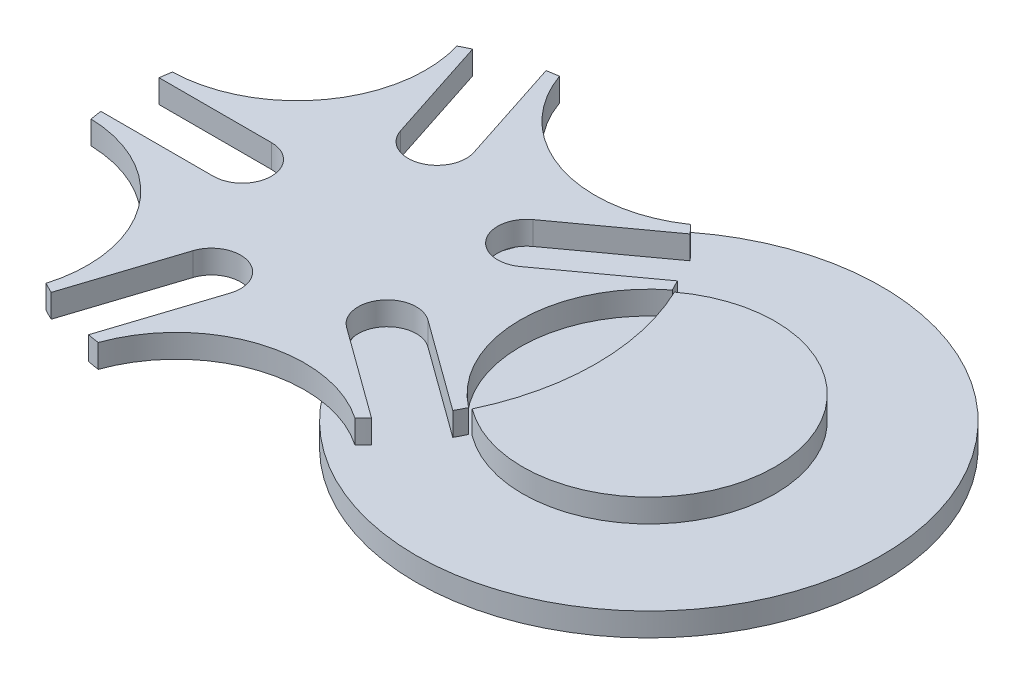
SolidWorks part; units mm, degrees
ref_plane "Front Plane" through (0, 0, 0) normal (0, 0, 1) x (1, 0, 0)
ref_plane "Top Plane" through (0, 0, 0) normal (0, 1, 0) x (1, 0, 0)
ref_plane "Right Plane" through (0, 0, 0) normal (1, 0, 0) x (0, 0, -1)
sketch "foundational triangle" plane through (0, 0, 0) normal (0, 1, 0) x (1, 0, 0)
  line L0 (0, 0) -> (20.549, 14.9297) construction
  line L1 (20.549, 14.9297) -> (31.3961, 0) construction
  line L2 (31.3961, 0) -> (0, 0) construction
  dimension "D1" = 90
  dimension "D2" = 25.4
  dimension "D3" = 36
sketch "main circles" plane through (0, 0, 0) normal (0, 1, 0) x (1, 0, 0)
  circle A0 centre (0, 0) radius 25.4
  circle A1 centre (31.3961, 0) radius 18.4542
  circle A2 centre (0, 0) radius 12.9419 construction
sketch "slot" plane through (0, 0, 0) normal (0, 1, 0) x (1, 0, 0)
  line L0 (20.549, 14.9297) -> (10.4703, 7.6071) construction
  line L1 (0, 0) -> (20.549, 14.9297) construction
  line L2 (22.4152, 12.3611) -> (12.3365, 5.0385)
  line L3 (18.6828, 17.4984) -> (8.604, 10.1757)
  arc A0 (22.4152, 12.3611) -> (18.6828, 17.4984) centre (20.549, 14.9297) ccw
  arc A1 (8.604, 10.1757) -> (12.3365, 5.0385) centre (10.4703, 7.6071) ccw
  circle A2 centre (0, 0) radius 12.9419 construction
  circle A3 centre (20.549, 14.9297) radius 3.175 construction
  circle A4 centre (10.4703, 7.6071) radius 3.175 construction
  point P5 (15.5096, 11.2684)
  dimension "D1" = 3.175
sketch "drivewheel construction lines" plane through (0, 0, 0) normal (0, 1, 0) x (1, 0, 0)
  line L0 (17.374, 14.9297) -> (17.374, 0) construction
  line L1 (31.3961, 0) -> (0, 0) construction
  circle A0 centre (20.549, 14.9297) radius 3.175 construction
  circle A1 centre (31.3961, 0) radius 14.0221
sketch "Sketch8" plane through (0, 0, 0) normal (0, 1, 0) x (1, 0, 0)
  circle A3 centre (31.3961, 0) radius 13.7681
  circle A4 centre (31.3961, 0) radius 13.7681 construction
  arc A5 (23.1602, 11.0332) -> (23.1602, -11.0332) centre (0, 0) cw
  circle A6 centre (0, 0) radius 25.654
  circle A7 centre (0, 0) radius 25.654 construction
  arc A8 (23.1602, 11.0332) -> (23.1602, -11.0332) centre (31.3961, 0) cw
  dimension "D1" = 0.254
  dimension "D2" = 0.254
extrude "drivewheel top" add sketch "Sketch8" along normal blind 2.54
sketch "5 slots" plane through (0, 0, 0) normal (0, 1, 0) x (1, 0, 0)
  line L0 (18.6828, 17.4984) -> (8.604, 10.1757) construction
  line L1 (18.6828, 17.4984) -> (8.604, 10.1757)
  line L2 (22.4152, 12.3611) -> (12.3365, 5.0385) construction
  line L3 (22.4152, 12.3611) -> (12.3365, 5.0385)
  line L4 (18.6828, -17.4984) -> (8.604, -10.1757)
  line L5 (22.4152, -12.3611) -> (12.3365, -5.0385)
  line L6 (-10.8686, -23.1757) -> (-7.0189, -11.3274)
  line L7 (-4.8294, -25.138) -> (-0.9797, -13.2897)
  line L8 (-25.4, 3.175) -> (-12.9419, 3.175)
  line L9 (-25.4, -3.175) -> (-12.9419, -3.175)
  line L10 (-4.8294, 25.138) -> (-0.9797, 13.2897)
  line L11 (-10.8686, 23.1757) -> (-7.0189, 11.3274)
  arc A0 (22.4152, 12.3611) -> (18.6828, 17.4984) centre (20.549, 14.9297) ccw construction
  arc A1 (22.4152, 12.3611) -> (18.6828, 17.4984) centre (20.549, 14.9297) ccw
  arc A2 (8.604, 10.1757) -> (12.3365, 5.0385) centre (10.4703, 7.6071) ccw construction
  arc A3 (8.604, 10.1757) -> (12.3365, 5.0385) centre (10.4703, 7.6071) ccw
  arc A4 (12.3365, -5.0385) -> (8.604, -10.1757) centre (10.4703, -7.6071) ccw
  arc A5 (18.6828, -17.4984) -> (22.4152, -12.3611) centre (20.549, -14.9297) ccw
  arc A6 (-0.9797, -13.2897) -> (-7.0189, -11.3274) centre (-3.9993, -12.3085) ccw
  arc A7 (-10.8686, -23.1757) -> (-4.8294, -25.138) centre (-7.849, -24.1568) ccw
  arc A8 (-12.9419, -3.175) -> (-12.9419, 3.175) centre (-12.9419, 0) ccw
  arc A9 (-25.4, 3.175) -> (-25.4, -3.175) centre (-25.4, 0) ccw
  arc A10 (-7.0189, 11.3274) -> (-0.9797, 13.2897) centre (-3.9993, 12.3085) ccw
  arc A11 (-4.8294, 25.138) -> (-10.8686, 23.1757) centre (-7.849, 24.1568) ccw
  point P32 (0, 0)
  dimension "D1" = 5
sketch "divots" plane through (0, 0, 0) normal (0, 1, 0) x (1, 0, 0)
  circle A0 centre (31.3961, 0) radius 14.0221 construction
  arc A1 (22.8413, 11.1101) -> (22.8413, -11.1101) centre (31.3961, 0) ccw
  circle A4 centre (0, 0) radius 25.4 construction
  arc A5 (17.6247, -18.2902) -> (-3.508, -25.1566) centre (9.7019, -29.8595) ccw
  arc A6 (-11.9487, -22.414) -> (-25.0094, -4.4375) centre (-25.4, -18.4542) ccw
  arc A7 (-25.0094, 4.4375) -> (-11.9487, 22.414) centre (-25.4, 18.4542) ccw
  arc A8 (-3.508, 25.1566) -> (17.6247, 18.2902) centre (9.7019, 29.8595) ccw
  circle A9 centre (0, 0) radius 25.4
  point P20 (0, 0)
  dimension "D1" = 5
extrude "Boss-Extrude4" add sketch "main circles" along normal blind 2.54 separate body contours A1 A0 | A0 A1 region at (19.3818, 0, 0) region at (-2.822, 0, 0)
extrude "Cut-Extrude4" cut sketch "5 slots" against normal blind 5.08 and the other way blind 2.54
extrude "Cut-Extrude6" cut sketch "divots" against normal blind 5.08 and the other way blind 5.08 contours A7 A9 | A8 A9 | A1 A9 | A5 A9 | A6 A9 region at (21.6264, 0, 0) region at (6.6829, 0, -20.5679) region at (6.6829, 0, 20.5679) region at (-17.4961, 0, -12.7117) region at (-17.4961, 0, 12.7117)
sketch "Sketch13" plane through (0, 0, 0) normal (0, 1, 0) x (1, 0, 0)
  line L0 (31.3961, 0) -> (0, 0) construction
  circle A0 centre (12.9419, 0) radius 3.175
  circle A1 centre (0, 0) radius 12.9419 construction
  circle A2 centre (31.3961, 0) radius 25.4
  dimension "D1" = 6.35
  dimension "D2" = 50.8
extrude "Boss-Extrude5" add sketch "Sketch13" against normal blind 2.54 separate body
equation "\"discdiam1\"= 1in"
equation "\"D3@Sketch1\"=\"discdiam1\""
equation "\"pin_diam\"= .25in"
equation "\"D4@Sketch1\"=\"pin_diam\"/2"
equation "\"D2@foundational triangle\" = \"discdiam1\""
equation "\"D1@slot\" = \"pin_diam\" / 2"
equation "\"D1@Sketch13\"=\"pin_diam\""
equation "\"D2@Sketch13\"=\"discdiam1\"*2"
